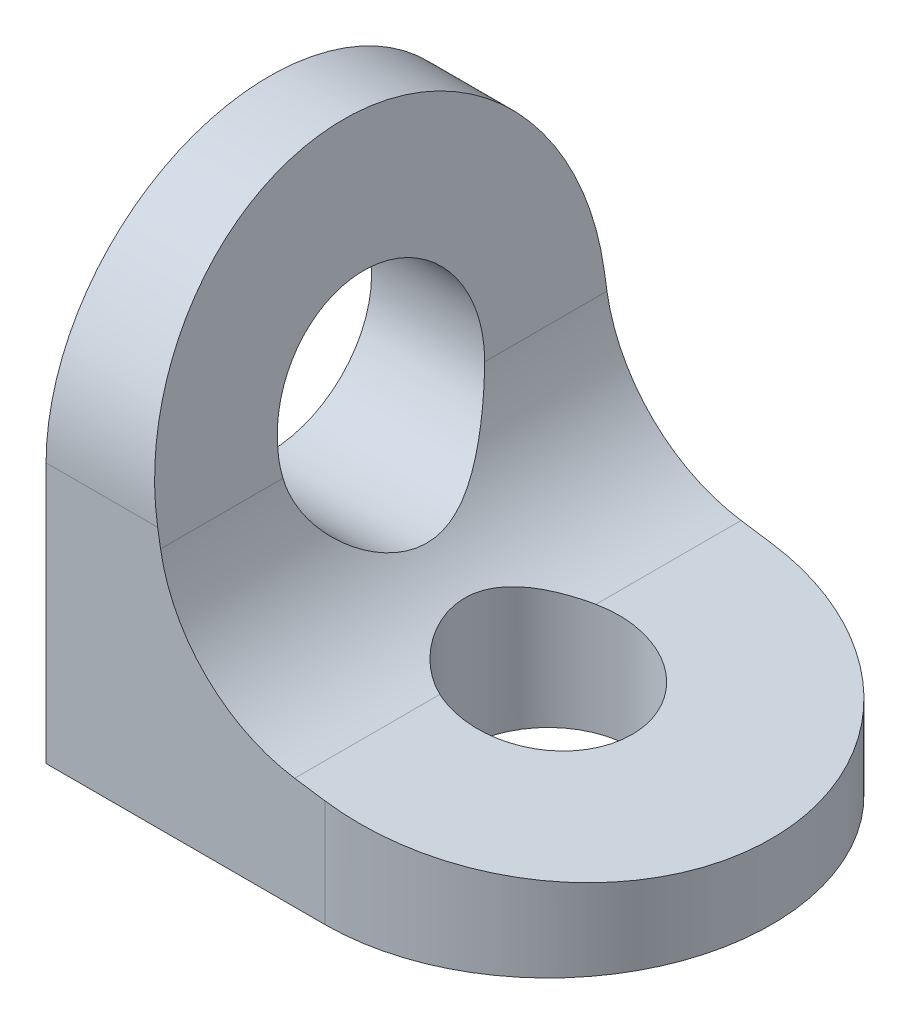
SolidWorks part; units mm, degrees
ref_plane "Plan de face" through (0, 0, 0) normal (0, 0, 1) x (1, 0, 0)
ref_plane "Plan de dessus" through (0, 0, 0) normal (0, 1, 0) x (1, 0, 0)
ref_plane "Plan de droite" through (0, 0, 0) normal (1, 0, 0) x (0, 0, -1)
sketch "Esquisse1" plane through (0, 0, 0) normal (0, 0, 1) x (1, 0, 0)
  line L0 (0, 0) -> (0, 13)
  line L1 (0, 13) -> (2, 13)
  line L2 (2, 13) -> (3.0774, 6.5356)
  line L3 (6.6826, 3) -> (13.5, 2)
  line L4 (13.5, 2) -> (13.5, 0)
  line L5 (13.5, 0) -> (0, 0)
  arc A1 (3.0774, 6.5356) -> (6.6826, 3) centre (7.3046, 7.2401) ccw
  point P7 (4.304, 4.1804)
  point P10 (7.5, 2.8801)
  point P15 (3, 7)
  dimension "D2" = 13
  dimension "D1" = 2
  dimension "D3" = 13.5
  dimension "D4" = 6
  dimension "D5" = 6
  dimension "D6" = 3
  dimension "D7" = 6
  dimension "D8" = 3
extrude "Boss.-Extru.1" add sketch "Esquisse1" along normal mid plane 12
fillet "Congé2" 2 edges at (1, 13, 6) (1, 13, -6) type full round first side face at (5.4549, 5.2783, 6) second side face at (5.4549, 5.2783, -6) middle face at (1, 13, 0)
fillet "Congé3" 2 edges at (13.5, 1, 6) (13.5, 1, -6) type full round first side face at (5.5977, 3.564, 6) second side face at (5.5977, 3.564, -6) middle face at (13.5, 1, 0)
sketch "Esquisse2" plane through (0, 0, 0) normal (0, -1, 0) x (1, 0, 0)
  circle A0 centre (7.5, 0) radius 2.25
  dimension "D1" = 4.5
extrude "Enlèv. mat.-Extru.1" cut sketch "Esquisse2" against normal through all
sketch "Esquisse3" plane through (0, 0, 0) normal (-1, 0, 0) x (0, 0, 1)
  circle A0 centre (0, 7) radius 2.75
  dimension "D1" = 5.5
extrude "Enlèv. mat.-Extru.2" cut sketch "Esquisse3" against normal through all
